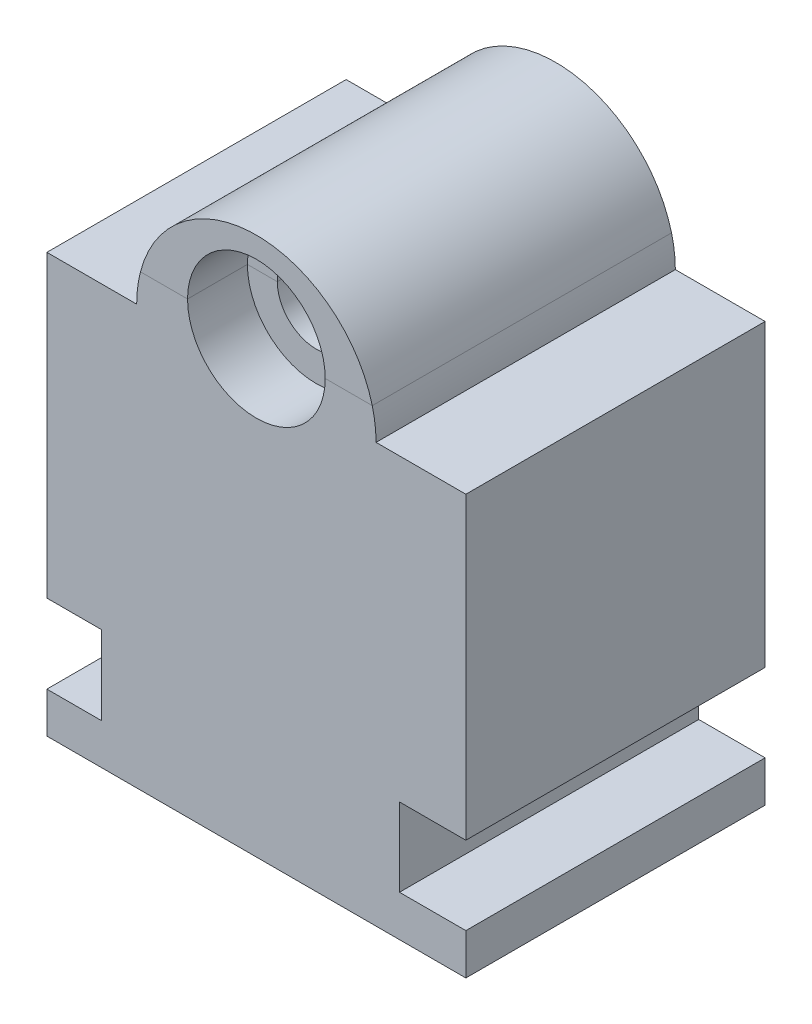
SolidWorks part; units mm, degrees
ref_plane "Plan de face" through (0, 0, 0) normal (0, 0, 1) x (1, 0, 0)
ref_plane "Plan de dessus" through (0, 0, 0) normal (0, 1, 0) x (1, 0, 0)
ref_plane "Plan de droite" through (0, 0, 0) normal (1, 0, 0) x (0, 0, -1)
sketch "Esquisse1" plane through (0, 0, 0) normal (0, 0, 1) x (1, 0, 0)
  line L0 (0, 0) -> (700, 0)
  line L1 (700, 0) -> (700, 450)
  line L2 (700, 450) -> (550, 450)
  line L3 (0, 0) -> (0, 450)
  line L4 (0, 450) -> (150, 450)
  arc A0 (550, 450) -> (150, 450) centre (350, 450) ccw
  dimension "D3" = 200
  dimension "D1" = 700
  dimension "D2" = 450
  dimension "D4" = 150
extrude "Boss.-Extru.1" add sketch "Esquisse1" along normal blind 500
sketch "Esquisse2" plane through (0, 0, 0) normal (0, -1, 0) x (1, 0, 0)
  line L0 (700, 500) -> (700, 0)
  line L1 (700, 0) -> (0, 0)
  line L2 (0, 0) -> (0, 500)
  line L3 (0, 500) -> (700, 500) construction
  line L4 (0, 500) -> (0, 0) construction
  line L5 (0, 500) -> (700, 500)
extrude "Boss.-Extru.2" add sketch "Esquisse2" along normal blind 250
sketch "Esquisse3" plane through (0, 0, 0) normal (0, 0, -1) x (-1, 0, 0)
  circle A0 centre (-350, 500) radius 65
extrude "Enlèv. mat.-Extru.1" cut sketch "Esquisse3" against normal blind 500
sketch "Esquisse4" plane through (0, 0, 0) normal (0, 0, -1) x (-1, 0, 0)
  line L0 (0, -50.3189) -> (-91.0727, -50.3189)
  line L1 (0, 450) -> (0, -250) construction
  line L2 (-91.0727, -50.3189) -> (-91.0727, -181.9886)
  line L3 (-91.0727, -181.9886) -> (0, -181.9886)
  line L4 (0, -181.9886) -> (0, -50.3189)
extrude "Enlèv. mat.-Extru.2" cut sketch "Esquisse4" against normal blind 500
sketch "Esquisse5" plane through (0, 0, 0) normal (0, 0, -1) x (-1, 0, 0)
  line L0 (-700, -181.4044) -> (-589.1123, -181.4044)
  line L1 (-700, -250) -> (-700, 450) construction
  line L2 (-589.1123, -181.4044) -> (-589.1123, -50.6587)
  line L3 (-589.1123, -50.6587) -> (-700, -50.6587)
  line L4 (-700, -50.6587) -> (-700, -181.4044)
extrude "Enlèv. mat.-Extru.3" cut sketch "Esquisse5" against normal blind 500
ref_plane "Plan1" through (0, 500, 0) normal (0, -1, 0) x (-1, 0, 0)
sketch "Esquisse6" plane through (0, 0, 500) normal (0, 0, 1) x (1, 0, 0)
  circle A0 centre (350, 500) radius 115
  circle A1 centre (350, 500) radius 65
extrude "Enlèv. mat.-Extru.4" cut sketch "Esquisse6" against normal blind 100
split "Fractionner2" trim tools "Plan1" bodies to split 108 resulting bodies 109 110
sketch "Esquisse7" plane through (0, 0, 0) normal (0, 0, -1) x (-1, 0, 0)
  circle A0 centre (-350, 500) radius 115
  circle A1 centre (-350, 500) radius 65
extrude "Enlèv. mat.-Extru.5" cut sketch "Esquisse7" against normal blind 100
